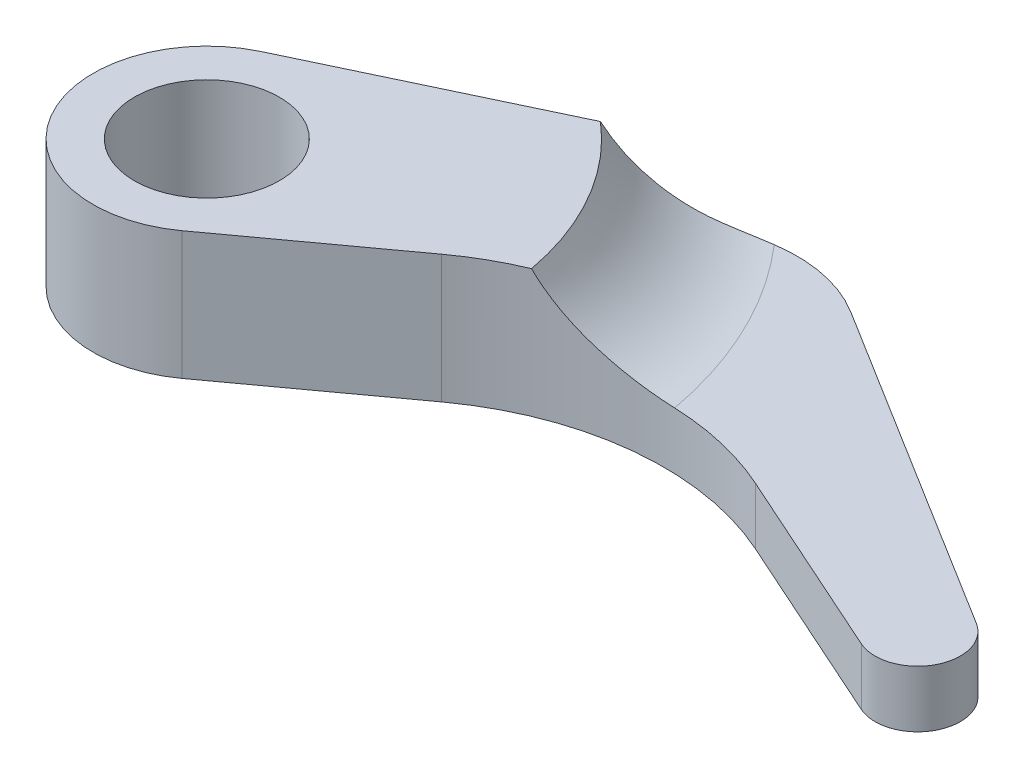
SolidWorks part; units mm, degrees
ref_plane "Front Plane" through (0, 0, 0) normal (0, 0, 1) x (1, 0, 0)
ref_plane "Top Plane" through (0, 0, 0) normal (0, 1, 0) x (1, 0, 0)
ref_plane "Right Plane" through (0, 0, 0) normal (1, 0, 0) x (0, 0, -1)
sketch "Sketch1" plane through (0, 0, 0) normal (0, 1, 0) x (1, 0, 0)
  line L0 (0, 0) -> (0, 20) construction
  line L1 (0, 0) -> (50, 0) construction
  line L9 (-3.4241, 7.2302) -> (23.5403, 20)
  line L10 (23.5403, 20) -> (51.5851, 2.5471)
  line L11 (4.7128, -6.4645) -> (24.6604, 8.0781)
  line L12 (24.6604, 8.0781) -> (48.7722, -2.7372)
  circle A0 centre (0, 0) radius 5.1
  arc A2 (-3.4241, 7.2302) -> (4.7128, -6.4645) centre (0, 0) ccw
  arc A8 (48.7722, -2.7372) -> (51.5851, 2.5471) centre (50, 0) ccw
  point P4 (24.6604, 8.0781)
  point P8 (23.1702, 15.1853)
  point P9 (23.5403, 20)
  dimension "D1" = 10.2
  dimension "D2" = 6
  dimension "D3" = 8
  dimension "D4" = 20
  dimension "D5" = 50
extrude "Boss-Extrude1" add sketch "Sketch1" along normal blind 9
sketch "Sketch3" plane through (0, 9, 0) normal (0, 1, 0) x (1, 0, 0)
  line L1 (69.061, 26.8013) -> (4.6381, 26.8013)
  line L2 (69.061, 26.8013) -> (69.061, -8.6199)
  line L3 (69.061, -8.6199) -> (17.6419, -8.6199)
  line L4 (4.6381, 26.8013) -> (4.6381, 19.0795)
  arc A0 (17.6419, -8.6199) -> (4.6381, 19.0795) centre (0, 0) ccw
  point P1 (4.6381, 13.1219)
extrude "Cut-Extrude1" cut sketch "Sketch3" against normal blind 5
fillet "Fillet2" radius 20 1 edges at (24.6604, 2, -8.0781)
fillet "Fillet3" radius 10 1 edges at (23.5403, 2, -20)
fillet "Fillet1" radius 10 1 edges at (17.0295, 4, -9.7742)
